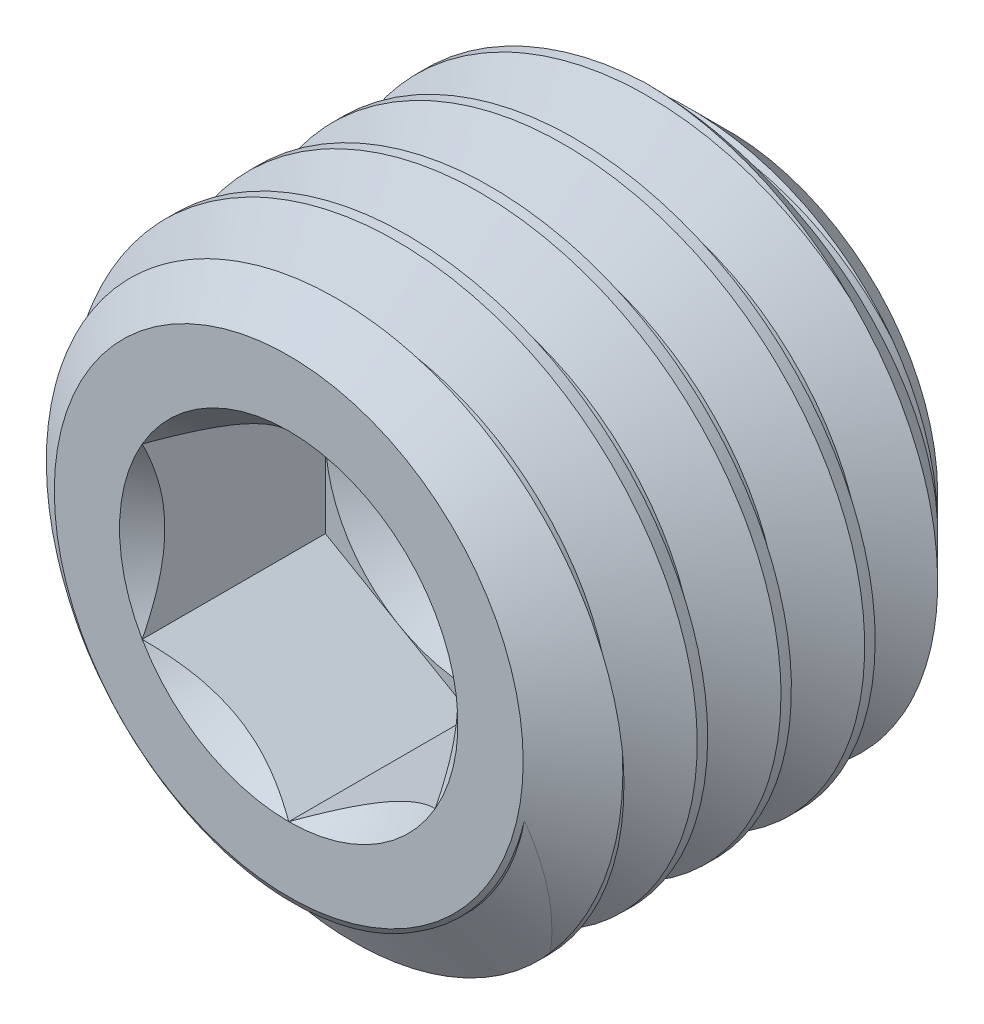
SolidWorks part; units mm, degrees
ref_plane "Front" through (0, 0, 0) normal (0, 0, 1) x (1, 0, 0)
ref_plane "Top" through (0, 0, 0) normal (0, 1, 0) x (1, 0, 0)
ref_plane "Right" through (0, 0, 0) normal (1, 0, 0) x (0, 0, -1)
sketch "Sketch22" plane through (0, 0, 0) normal (1, 0, 0) x (0, 0, -1)
  line L0 (-2.3813, 0) -> (-2.3813, 2.54)
  line L1 (-2.3813, 2.54) -> (-1.9366, 3.175)
  line L2 (-1.9366, 3.175) -> (1.4741, 3.175)
  line L3 (1.4741, 3.175) -> (2.3813, 2.2679)
  line L4 (-0.2313, 3.175) -> (-0.2313, -3.175) construction
  line L5 (2.3813, 0) -> (-2.3813, 0)
  line L7 (2.3813, 0) -> (2.3813, 2.2679)
  line L10 (-2.3813, 2.54) -> (-2.3813, -2.54) construction
  point P13 (-0.2313, 0)
  dimension "Length" = 4.7625
  dimension "D3" = 35
  dimension "D1" = 5.08
  dimension "Dia" = 6.35
  dimension "D2" = 0.9071
  dimension "D4" = 45
revolve "Revolve1" add sketch "Sketch22" angle 360 about L5
ref_plane "Plane1" through (0, 0, -2.3813) normal (0, 0, 1) x (1, 0, 0)
sketch "Sketch27" plane through (0, 0, -2.3813) normal (0, 0, 1) x (1, 0, 0)
  circle A0 centre (0, 0) radius 3.175 construction
  circle A1 centre (0, 0) radius 3.175
curve "Helix/Spiral1" pitch 0.9071 height 5.6696 radius 3.175 centre (0, 0, -2.3813) axis (0, 0, 1) start towards (1, 0, 0)
sketch "Sketch23" plane through (0, 0, 2.3813) normal (0, 0, 1) x (1, 0, 0)
  line L1 (0, 1.8331) -> (-1.5875, 0.9165)
  line L2 (-1.5875, 0.9165) -> (-1.5875, -0.9165)
  line L3 (-1.5875, -0.9165) -> (0, -1.8331)
  line L4 (0, -1.8331) -> (1.5875, -0.9165)
  line L5 (1.5875, -0.9165) -> (1.5875, 0.9165)
  line L6 (1.5875, 0.9165) -> (0, 1.8331)
  circle A0 centre (0, 0) radius 1.5875 construction
  dimension "Hex" = 3.175
extrude "Cut-Extrude10" cut sketch "Sketch23" against normal blind 1.9844
sketch "Sketch24" plane through (0, 0, 2.3813) normal (0, 0, 1) x (1, 0, 0)
  circle A0 centre (0, 0) radius 1.8331
extrude "Cut-Extrude11" cut sketch "Sketch24" against normal through all draft 45
sketch "Sketch26" plane through (0, 0, 0.3969) normal (0, 0, 1) x (1, 0, 0)
  circle A0 centre (0, 0) radius 1.5875 construction
  circle A1 centre (0, 0) radius 1.5875
extrude "Cut-Extrude12" cut sketch "Sketch26" against normal through all draft 60
sketch "Sketch30" plane through (0, 0, 0) normal (1, 0, 0) x (0, 0, -1)
  line L0 (-1.9366, 3.175) -> (1.4741, 3.175) construction
  line L1 (-2.3813, 0) -> (-2.3813, 2.54) construction
  line L2 (2.3813, 0) -> (2.3813, 2.2679) construction
  point P0 (-2.3813, 3.175)
  point P1 (2.3813, 3.175)
  point P2 (2.3813, -3.175)
  point P11 (0.1134, -3.175)
  dimension "D1" = 2.2679
sketch "Sketch28" plane through (0, 0, 0) normal (1, 0, 0) x (0, 0, -1)
  line L0 (2.3813, 3.175) -> (3.175, 3.175)
  line L1 (3.175, 3.175) -> (2.8348, 2.5858)
  line L2 (2.8348, 2.5858) -> (2.7214, 2.5858)
  line L3 (2.7214, 2.5858) -> (2.3813, 3.175)
  line L4 (2.5513, 2.8804) -> (3.0049, 2.8804) construction
  line L6 (-1.9366, 3.175) -> (1.4741, 3.175) construction
  line L7 (2.3813, 3.4925) -> (2.3813, -3.4925) construction
  dimension "D1" = 0.1134
  dimension "D3" = 60
  dimension "D2" = 0.4536
sweep "Cut-Sweep2" cut profiles "Sketch28" path "Helix/Spiral1"
ref_axis "Center Axis 1" through (0, 0, -2.3813) along (0, 0, 1)
ref_plane "Contact Plane 1" through (0, 0, -2.3813) normal (0, 0, -1) x (-1, 0, 0)
equation "\"D1@Sketch28\" = \"D4@Helix/Spiral1\" * .125"
equation "\"D3@Helix/Spiral1\" = \"Length@Sketch22\" + \"D4@Helix/Spiral1\""
equation "\"D1@Sketch30\" = \"D4@Helix/Spiral1\" * 2.5"
equation "\"hex Depth@Cut-Extrude10\" = \"Hex@Sketch23\" * .625"
equation "\"D2@Sketch28\" = \"D4@Helix/Spiral1\" * .5"
equation "\"D1@Sketch22\" = \"Dia@Sketch22\" * .8"
equation "\"D2@Sketch22\" = \"D4@Helix/Spiral1\""
